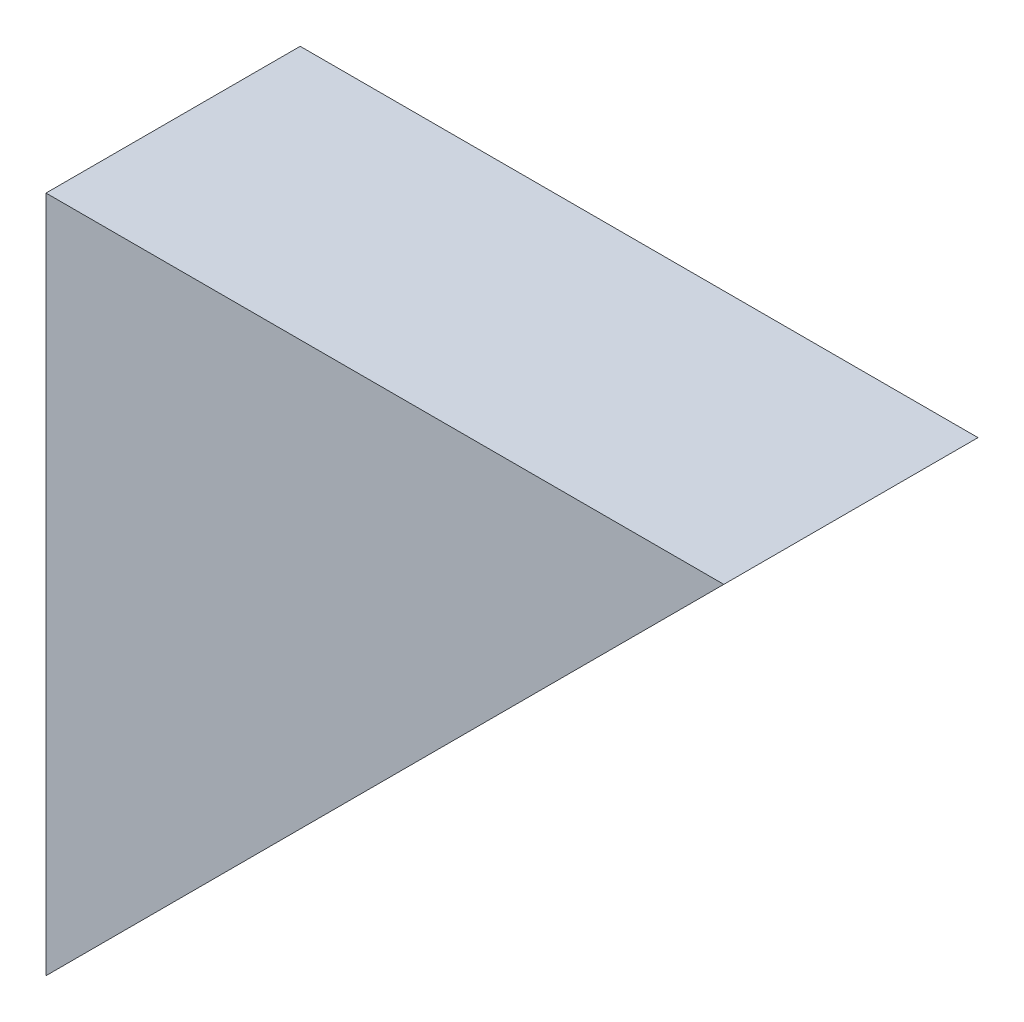
SolidWorks part; units mm, degrees
material "Cedar"
ref_plane "Front Plane" through (0, 0, 0) normal (0, 0, 1) x (1, 0, 0)
ref_plane "Top Plane" through (0, 0, 0) normal (0, 1, 0) x (1, 0, 0)
ref_plane "Right Plane" through (0, 0, 0) normal (1, 0, 0) x (0, 0, -1)
sketch "Sketch1" plane through (0, 0, 0) normal (0, 0, 1) x (1, 0, 0)
  line L0 (0, 0) -> (101.6, 101.6)
  line L1 (101.6, 101.6) -> (0, 101.6)
  line L2 (0, 101.6) -> (0, 0)
  dimension "D1" = 101.6
extrude "Boss-Extrude1" add sketch "Sketch1" along normal blind 19.05 and the other way blind 19.05
